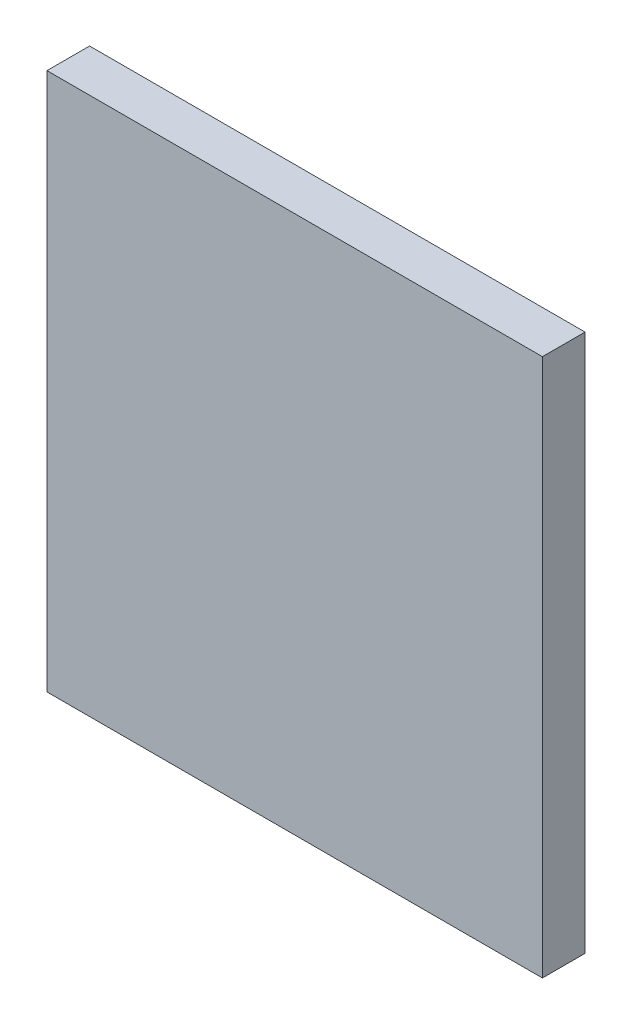
SolidWorks part; units mm, degrees
ref_plane "Front Plane" through (0, 0, 0) normal (0, 0, 1) x (1, 0, 0)
ref_plane "Top Plane" through (0, 0, 0) normal (0, 1, 0) x (1, 0, 0)
ref_plane "Right Plane" through (0, 0, 0) normal (1, 0, 0) x (0, 0, -1)
sketch "Sketch1" plane through (0, 0, 0) normal (0, 0, 1) x (1, 0, 0)
  line L1 (23.25, -25.25) -> (-23.25, -25.25)
  line L2 (23.25, -25.25) -> (23.25, 25.25)
  line L3 (23.25, 25.25) -> (-23.25, 25.25)
  line L4 (-23.25, -25.25) -> (-23.25, 25.25)
  line L5 (23.25, -25.25) -> (-23.25, 25.25) construction
  line L6 (23.25, 25.25) -> (-23.25, -25.25) construction
  point P0 (0, 0)
  point P5 (0, 0)
  dimension "D1" = 46.5
  dimension "D2" = 50.5
extrude "Boss-Extrude1" add sketch "Sketch1" along normal blind 4
sketch "Sketch2" plane through (0, 0, 4) normal (0, 0, 1) x (1, 0, 0)
  line L10 (-23.25, 13.6217) -> (23.25, 13.6217) construction
  line L15 (-23.25, 25.25) -> (-23.25, -25.25) construction
  line L16 (23.25, -25.25) -> (23.25, 25.25) construction
